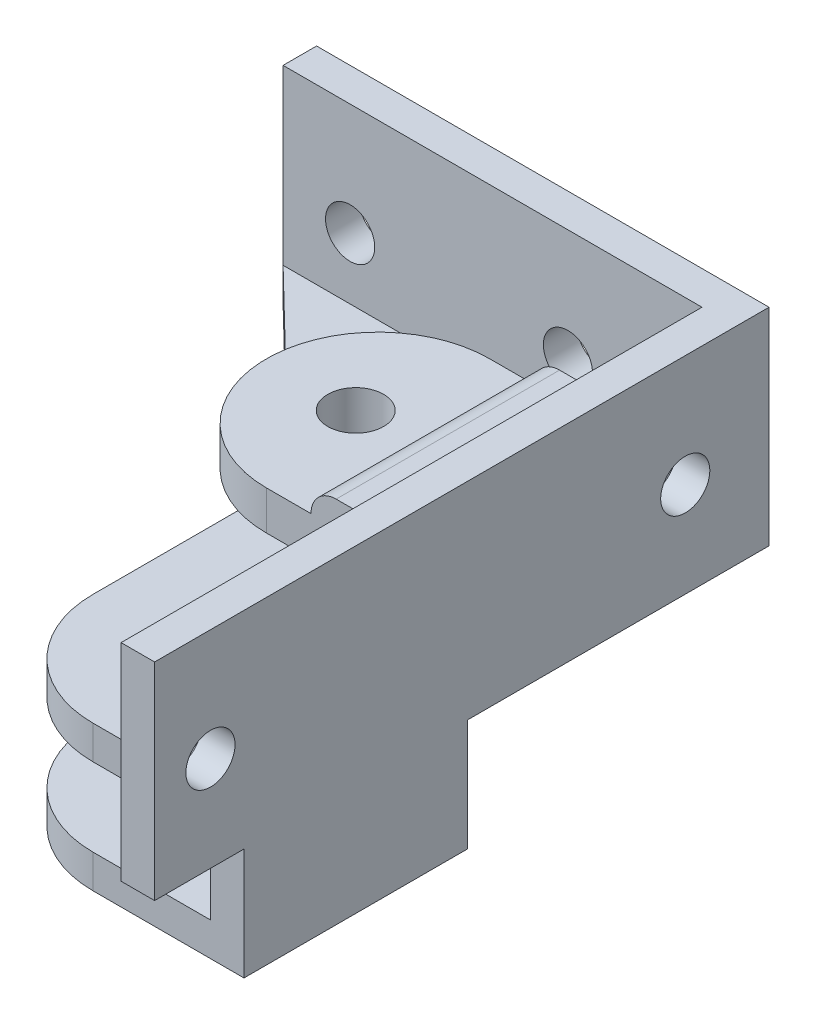
SolidWorks part; units mm, degrees
material "ABS"
ref_plane "Front Plane" through (0, 0, 0) normal (0, 0, 1) x (1, 0, 0)
ref_plane "Top Plane" through (0, 0, 0) normal (0, 1, 0) x (1, 0, 0)
ref_plane "Right Plane" through (0, 0, 0) normal (1, 0, 0) x (0, 0, -1)
sketch "Sketch1" plane through (0, 0, 0) normal (0, 1, 0) x (1, 0, 0)
  line L0 (-40.5, 0) -> (0, 0)
  line L1 (0, 0) -> (0, -55)
  line L2 (0, -55) -> (-3, -55)
  line L3 (-3, -55) -> (-3, -3)
  line L4 (-3, -3) -> (-40.5, -3)
  line L5 (-40.5, -3) -> (-40.5, 0)
  dimension "D1" = 3
  dimension "D2" = 40.5
  dimension "D3" = 55
extrude "Boss-Extrude1" add sketch "Sketch1" along normal blind 18.5
sketch "Sketch2" plane through (0, 0, 0) normal (0, -1, 0) x (1, 0, 0)
  line L0 (-40.5, 3) -> (-23.5, 19.5)
  line L1 (-23.5, 19.5) -> (-23.5, 37)
  line L2 (-13.5, 47) -> (-3, 47)
  line L3 (-3, 3) -> (-3, 55) construction
  line L4 (-3, 47) -> (-3, 3)
  line L5 (-3, 3) -> (-40.5, 3)
  line L6 (0, 0) -> (-40.5, 0) construction
  line L7 (-3, 55) -> (0, 55) construction
  arc A0 (-23.5, 37) -> (-13.5, 47) centre (-13.5, 37) cw
  dimension "D3" = 10
  dimension "D1" = 19.5
  dimension "D2" = 17
  dimension "D4" = 8
extrude "Boss-Extrude2" add sketch "Sketch2" against normal blind 3
sketch "Sketch3" plane through (0, 3, 0) normal (0, 1, 0) x (1, 0, 0)
  line L0 (-3, -31.5) -> (-13.5, -31.5)
  line L1 (-3, -3) -> (-3, -47) construction
  line L2 (-13.5, -11.5) -> (-3, -11.5)
  line L3 (-3, -11.5) -> (-3, -31.5)
  line L4 (-40.5, -3) -> (-3, -3) construction
  arc A0 (-13.5, -31.5) -> (-13.5, -11.5) centre (-13.5, -21.5) cw
  dimension "D1" = 20
  dimension "D2" = 8.5
  dimension "D3" = 20.5
extrude "Boss-Extrude3" add sketch "Sketch3" along normal blind 3.5 from offset 7
sketch "Sketch4" plane through (0, 0, 31.5) normal (0, 0, 1) x (1, 0, 0)
  line L0 (-3, 13.5) -> (-3, 15.75)
  line L1 (-3, 15.75) -> (-9.5, 15.75)
  line L2 (-9.5, 15.75) -> (-9.5, 13.5)
  line L4 (-9.5, 13.5) -> (-3, 13.5)
  dimension "D1" = 6.5
  dimension "D2" = 2.25
extrude "Boss-Extrude4" add sketch "Sketch4" against normal up to surface (20 mm away) up to face at (-8.25, 11.75, 11.5)
fillet "Fillet1" radius 2.25 1 edges at (-9.5, 15.75, 21.5)
sketch "Sketch5" plane through (0, 0, 0) normal (0, -1, 0) x (1, 0, 0)
  line L0 (0, 47) -> (0, 27)
  line L1 (0, 55) -> (0, 0) construction
  line L2 (0, 27) -> (-9, 27)
  line L3 (-9, 27) -> (-9, 29)
  line L4 (-9, 29) -> (-3, 29)
  line L5 (-3, 29) -> (-3, 47)
  line L6 (-3, 47) -> (0, 47)
  line L7 (-3, 55) -> (0, 55) construction
  line L8 (-3, 47) -> (-3, 55) construction
  dimension "D1" = 20
  dimension "D2" = 8
  dimension "D3" = 2
  dimension "D4" = 9
extrude "Boss-Extrude5" add sketch "Sketch5" along normal blind 7
sketch "Sketch6" plane through (0, -7, 0) normal (0, -1, 0) x (1, 0, 0)
  line L0 (0, 27) -> (0, 47)
  line L1 (0, 47) -> (-13.5, 47)
  line L2 (-13.5, 27) -> (0, 27)
  arc A0 (-13.5, 47) -> (-13.5, 27) centre (-13.5, 37) ccw
  dimension "D1" = 23.5
extrude "Boss-Extrude6" add sketch "Sketch6" along normal blind 3
sketch "Sketch7" plane through (0, 13.5, 0) normal (0, 1, 0) x (1, 0, 0)
  line L0 (0, -55) -> (0, 0) construction
  line L1 (-3, -47) -> (-13.5, -47) construction
  circle A0 centre (-15.5, -21.5) radius 2.5
  circle A1 centre (-15.5, -37) radius 2.5
  dimension "D1" = 5
  dimension "D2" = 15.5
  dimension "D3" = 15.5
  dimension "D4" = 10
extrude "Cut-Extrude1" cut sketch "Sketch7" against normal through all
sketch "Sketch8" plane through (0, 0, 0) normal (1, 0, 0) x (0, 0, -1)
  line L0 (-55, 18.5) -> (0, 18.5) construction
  line L1 (0, 18.5) -> (0, 0) construction
  circle A0 centre (-50, 8.5) radius 2.2
  circle A1 centre (-7.5, 8.5) radius 2.2
  dimension "D1" = 4.4
  dimension "D2" = 42.5
  dimension "D3" = 10
  dimension "D4" = 7.5
extrude "Cut-Extrude2" cut sketch "Sketch8" against normal through all
sketch "Sketch9" plane through (0, 0, 0) normal (0, 0, -1) x (-1, 0, 0)
  line L0 (0, 18.5) -> (40.5, 18.5) construction
  line L1 (40.5, 18.5) -> (40.5, 0) construction
  circle A0 centre (15, 8.5) radius 2.2
  circle A1 centre (34.5, 8.5) radius 2.2
  dimension "D1" = 10
  dimension "D2" = 19.5
  dimension "D3" = 4.4
  dimension "D4" = 6
extrude "Cut-Extrude3" cut sketch "Sketch9" against normal up to next
sketch "Sketch10" plane through (0, -7, 0) normal (0, 1, 0) x (1, 0, 0)
  circle A0 centre (-15.5, -37) radius 2.5
  circle A1 centre (-15.5, -37) radius 3.5
  dimension "D1" = 5
  dimension "D2" = 7
extrude "Boss-Extrude7" add sketch "Sketch10" along normal up to next
sketch "Sketch11" plane through (0, 3, 0) normal (0, 1, 0) x (1, 0, 0)
  circle A0 centre (-15.5, -21.5) radius 3.5
  circle A1 centre (-15.5, -21.5) radius 2.5 construction
  circle A2 centre (-15.5, -21.5) radius 2.5
  dimension "D1" = 7
extrude "Boss-Extrude8" add sketch "Sketch11" along normal up to next
sketch "Sketch12" plane through (0, 0, 47) normal (0, 0, 1) x (1, 0, 0)
  line L0 (-12, -7) -> (-12, 0) construction
  line L1 (-12, -1) -> (-19, -1)
  line L2 (-12, -1) -> (-12, -6)
  line L3 (-12, -6) -> (-19, -6)
  line L4 (-19, -1) -> (-19, -6)
  line L5 (-19, 0) -> (-19, -7) construction
  line L6 (-12, 3) -> (-12, 10) construction
  line L7 (-12, 9) -> (-19, 9)
  line L8 (-12, 9) -> (-12, 4)
  line L9 (-12, 4) -> (-19, 4)
  line L10 (-19, 9) -> (-19, 4)
  line L11 (-19, 10) -> (-19, 3) construction
  line L12 (-19, 6.5) -> (-12, 6.5) construction
  line L13 (-19, -3.5) -> (-12, -3.5) construction
  dimension "D1" = 5
  dimension "D2" = 5
extrude "Cut-Extrude4" cut sketch "Sketch12" against normal up to surface (44 mm away) up to face at (-36.7, 8.5, 3)
